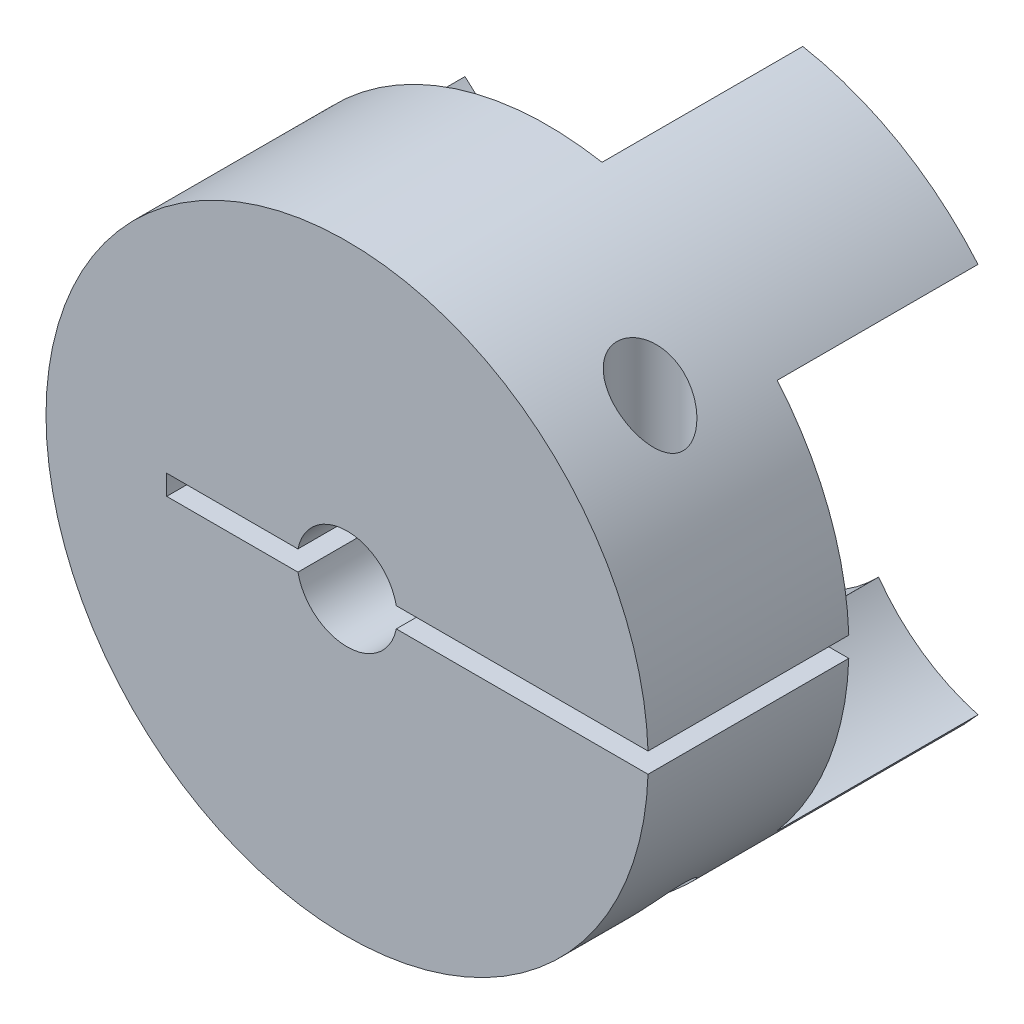
SolidWorks part; units mm, degrees
ref_plane "Front Plane" through (0, 0, 0) normal (0, 0, 1) x (1, 0, 0)
ref_plane "Top Plane" through (0, 0, 0) normal (0, 1, 0) x (1, 0, 0)
ref_plane "Right Plane" through (0, 0, 0) normal (1, 0, 0) x (0, 0, -1)
sketch "Sketch1" plane through (0, 0, 0) normal (0, 0, 1) x (1, 0, 0)
  line L0 (20.2245, 0) -> (-20.2245, 0) construction
  circle A0 centre (0, 0) radius 15
  arc A1 (-8.6501, 2.485) -> (-8.6501, -2.485) centre (0, 0) ccw
  arc A2 (-8.6501, 2.485) -> (-14.1279, 5.04) centre (-7.8056, 11.4453) cw
  arc A3 (-8.6501, -2.485) -> (-14.1279, -5.04) centre (-7.8056, -11.4453) ccw
  arc A4 (6.4771, 6.2487) -> (11.4287, 9.7151) centre (13.8147, 1.0372) cw
  arc A5 (2.173, 8.7337) -> (2.6992, 14.7551) centre (-6.0091, 12.4825) ccw
  arc A6 (2.173, -8.7337) -> (2.6992, -14.7551) centre (-6.0091, -12.4825) cw
  arc A7 (6.4771, -6.2487) -> (11.4287, -9.7151) centre (13.8147, -1.0372) ccw
  arc A8 (6.4771, 6.2487) -> (2.173, 8.7337) centre (0, 0) ccw
  arc A9 (2.173, -8.7337) -> (6.4771, -6.2487) centre (0, 0) ccw
  point P7 (0, 0)
  point P13 (0, 0)
  point P14 (0, 0)
  point P15 (0, 0)
  point P28 (0, 0)
  point P29 (0, 0)
  dimension "D1" = 30
  dimension "D2" = 18
  dimension "D3" = 9
  dimension "D4" = 4.97
  dimension "D5" = 10.08
  dimension "D6" = 3
extrude "Boss-Extrude1" add sketch "Sketch1" along normal blind 10 contours A0 L0 A1 A3 A6 A9 A7 | A1 L0 A0 A3 | L0 A1 A2 A0 | L0 A0 A4 A8 A5 A2 A1 | A8 A4 A0 A5 | A9 A6 A0 A7 region at (0, -6.0913, 0) region at (0, 6.0913, 0) region at (-12.1953, -1.8096, 0) region at (-12.1953, 1.8096, 0) region at (6.0977, 10.5615, 0) region at (6.0977, -10.5615, 0)
extrude "Boss-Extrude2" add sketch "Sketch1<3>" against normal blind 10 contours L0 A1 A2 A0 | A1 L0 A0 A3 | A9 A6 A0 A7 | A8 A4 A0 A5 region at (-12.1953, -1.8096, 0) region at (-12.1953, 1.8096, 0) region at (6.0977, 10.5615, 0) region at (6.0977, -10.5615, 0)
sketch "Sketch1<3>" plane through (0, 0, 0) normal (0, 0, 1) x (1, 0, 0) same geometry as "Sketch1"
sketch "Sketch2" plane through (0, 0, 0) normal (0, 0, -1) x (-1, 0, 0)
  line L0 (-14.9917, -0.5) -> (14.9917, -0.5)
  line L1 (11, 0) -> (-11, 0) construction
  line L2 (-14.9917, 0.5) -> (14.9917, 0.5)
  arc A0 (-2.4495, -0.5) -> (2.4495, -0.5) centre (0, 0) ccw
  circle A1 centre (0, 0) radius 15 construction
  circle A2 centre (0, 0) radius 15
  arc A3 (2.4495, 0.5) -> (-2.4495, 0.5) centre (0, 0) ccw
  arc M8 (-11.4287, 9.7151) -> (-11.4287, -9.7151) centre (0, 0) ccw
  arc M14 (8.6501, -2.485) -> (8.6501, 2.485) centre (0, 0) ccw
  dimension "D1" = 5
  dimension "D2" = 1
extrude "Cut-Extrude1" cut sketch "Sketch2" against normal blind 10 contours L2 L0 M8 M14 | L2 A3 | L0 A0 region at (3.0009, 0, 0) region at (0, -1.3359, 0) region at (0, 1.3359, 0)
hole_wizard "M4x0.7 Tapped Hole1" positions "3DSketch2" profile "Sketch4" tap size "M4x0.7" standard "ANSI Metric" end condition through all
sketch3d "3DSketch2"
  line L0 (14.9917, 0.5, 0) -> (2.4495, 0.5, 0) construction
  line L1 (14.9917, -0.5, 10) -> (14.9917, -0.5, 0) construction
  point P0 (10.0927, 0.5, 5)
  dimension "D1" = 5
  dimension "D2" = 5
cosmetic thread "Hole Thread1" parameters "D2"=4
sketch "Sketch4" plane through (10.0927, 0.5, 5) normal (1, 0, 0) x (0, 0, -1)
  line L0 (0, 0) -> (0, 14.5)
  line L1 (0, 14.5) -> (1.65, 14.5)
  line L2 (1.65, 14.5) -> (1.65, 0)
  line L5 (1.65, 0) -> (0, 0)
  line L11 (0, -6.35) -> (0, 107.95) construction
  dimension "Thru Tap Drill Dia." = 3.3
  dimension "Thru Tap Drill Depth" = 14.5
hole_wizard "M4x0.7 Tapped Hole2" positions "Sketch5" profile "Sketch6" tap size "M4x0.7" standard "ANSI Metric" end condition through all
sketch "Sketch5" plane through (0, -0.5, 0) normal (0, 1, 0) x (1, 0, 0)
  point P0 (10.0927, -5)
sketch "Sketch6" plane through (10.0927, -0.5, 5) normal (1, 0, 0) x (0, 0, 1)
  line L0 (0, 0) -> (0, 14.5)
  line L1 (0, 14.5) -> (1.65, 14.5)
  line L2 (1.65, 14.5) -> (1.65, 0)
  line L5 (1.65, 0) -> (0, 0)
  line L11 (0, -6.35) -> (0, 107.95) construction
  dimension "Thru Tap Drill Dia." = 3.3
  dimension "Thru Tap Drill Depth" = 14.5
cosmetic thread "Hole Thread2" parameters "D2"=4
